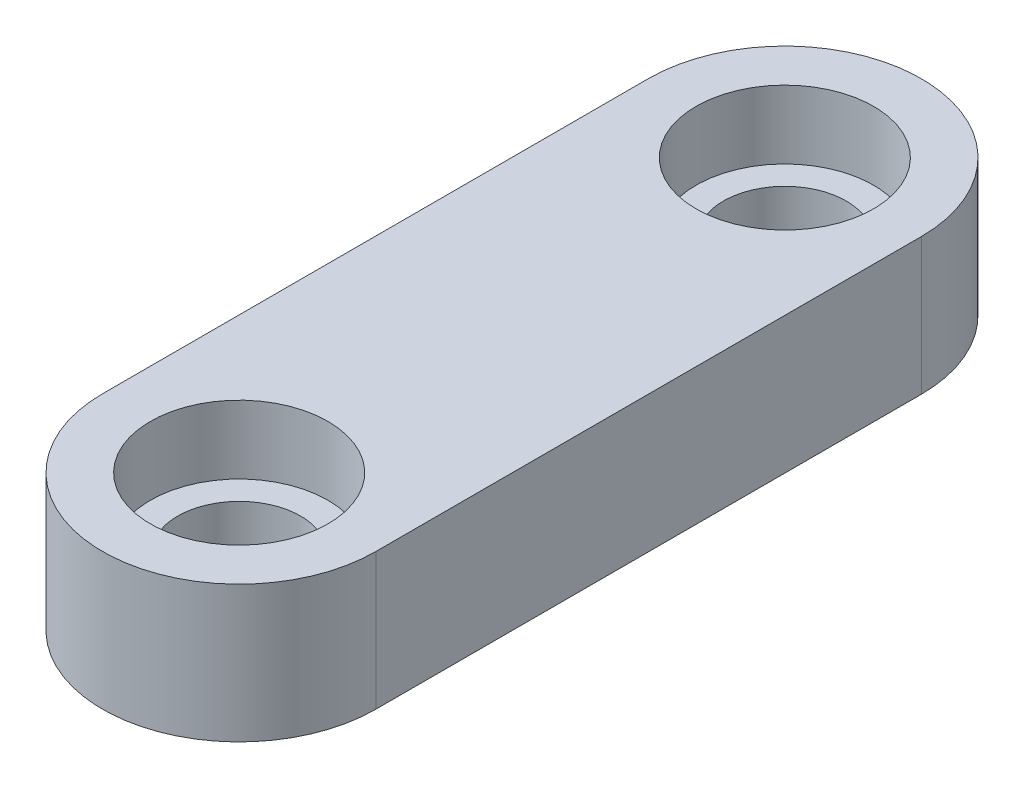
SolidWorks part; units mm, degrees
ref_plane "정면" through (0, 0, 0) normal (0, 0, 1) x (1, 0, 0)
ref_plane "윗면" through (0, 0, 0) normal (0, 1, 0) x (1, 0, 0)
ref_plane "우측면" through (0, 0, 0) normal (1, 0, 0) x (0, 0, -1)
sketch "스케치1" plane through (0, 0, 0) normal (0, 0, 1) x (1, 0, 0)
  line L1 (-10, -5) -> (10, -5)
  line L2 (-10, -5) -> (-10, 5)
  line L3 (-10, 5) -> (10, 5)
  line L4 (10, -5) -> (10, 5)
  line L5 (-10, -5) -> (10, 5) construction
  line L6 (-10, 5) -> (10, -5) construction
  point P0 (0, 0)
  dimension "D1" = 10
  dimension "D2" = 20
extrude "보스-돌출1" add sketch "스케치1" along normal blind 59.9396
sketch "스케치2" plane through (0, 5, 0) normal (0, 1, 0) x (1, 0, 0)
  line L0 (10, 0) -> (-10, 0) construction
  circle A0 centre (0, -10) radius 6.5
  dimension "D1" = 13
  dimension "D2" = 10
extrude "컷-돌출1" cut sketch "스케치2" against normal blind 5
ref_plane "평면1" through (0, 0, 29.9698) normal (0, 0, 1) x (1, 0, 0)
sketch "스케치3" plane through (0, 5, 0) normal (0, 1, 0) x (1, 0, 0)
  line L0 (-22.6352, -10) -> (28.5035, -10) construction
  line L1 (-21.2621, -10) -> (-10, -10)
  line L2 (10, -10) -> (21.2621, -10)
  circle A0 centre (0, -10) radius 4.5
  circle A1 centre (0, -10) radius 6.5
  circle A2 centre (0, -10) radius 6.5 construction
  arc A3 (10, -10) -> (-10, -10) centre (0, -10) ccw
  arc A4 (21.2621, -10) -> (-21.2621, -10) centre (0, -10) ccw
  line M5 (10, 0) -> (-10, 0)
  line M6 (-10, 0) -> (-10, -59.9396)
  line M8 (10, -59.9396) -> (10, 0)
  dimension "D2" = 9
  dimension "D1" = 0
extrude "컷-돌출2" cut sketch "스케치3" against normal blind 20 contours A0
extrude "컷-돌출3" cut sketch "스케치3<4>" against normal blind 10 contours A3 M5 M6 | A3 M8 M5 region at (-7.7663, 5, 2.2337) region at (7.7663, 5, 2.2337)
sketch "스케치3<4>" plane through (0, 5, 0) normal (0, 1, 0) x (1, 0, 0) same geometry as "스케치3"
mirror "대칭 복사1" about plane through (0, 0, 29.9698) normal (0, 0, 1) of "컷-돌출3", "컷-돌출1", "컷-돌출2"
sketch "스케치4" plane through (0, -5, 0) normal (0, 1, 0) x (1, 0, 0)
  line L0 (-2.4755, -38.1181) -> (-10, -33.7738)
  line L2 (0, -5.5) -> (0, 5.5) construction
  line L3 (-10, -49.9396) -> (-10, -10) construction
  line L4 (-10, -33.7738) -> (-10, -29.7476)
  line L7 (0, -49.9396) -> (-13.5316, -42.1271) construction
  line L8 (0, -29.7476) -> (-10, -29.7476)
  line L11 (-2.4755, -33.8404) -> (0, -33.8404)
  line L12 (0, -29.7476) -> (0, -33.8404)
  line L13 (-2.4755, -33.8404) -> (-2.4755, -38.1181)
  circle A2 centre (0, -49.9396) radius 4.5 construction
  dimension "D1" = 120
  dimension "D2" = 9
extrude "보스-돌출2" add sketch "스케치4" against normal blind 5
sketch "스케치5" plane through (0, -5, 0) normal (0, -1, 0) x (1, 0, 0)
  line L1 (-7, 29.7476) -> (-3.8916, 29.7476)
  line L2 (-7, 29.7476) -> (-7, 21.7476)
  line L3 (-7, 21.7476) -> (-3.8916, 21.7476)
  line L4 (-3.8916, 29.7476) -> (-3.8916, 21.7476)
  line L5 (-10, 29.7476) -> (-10, 10) construction
  dimension "D1" = 8
  dimension "D2" = 3
extrude "컷-돌출4" cut sketch "스케치5" against normal blind 8
sketch "스케치7" plane through (-7, 0, 0) normal (1, 0, 0) x (0, 0, -1)
  line L0 (-25.7476, -5) -> (-25.7476, 3) construction
  line L1 (-29.7476, -5) -> (-21.7476, -5) construction
  line L2 (-29.7476, 3) -> (-21.7476, 3) construction
  circle A0 centre (-23.6893, -1) radius 1.25
  circle A1 centre (-27.8059, -1) radius 1.25
  dimension "D1" = 2.5
extrude "컷-돌출5" cut sketch "스케치7" against normal blind 8
